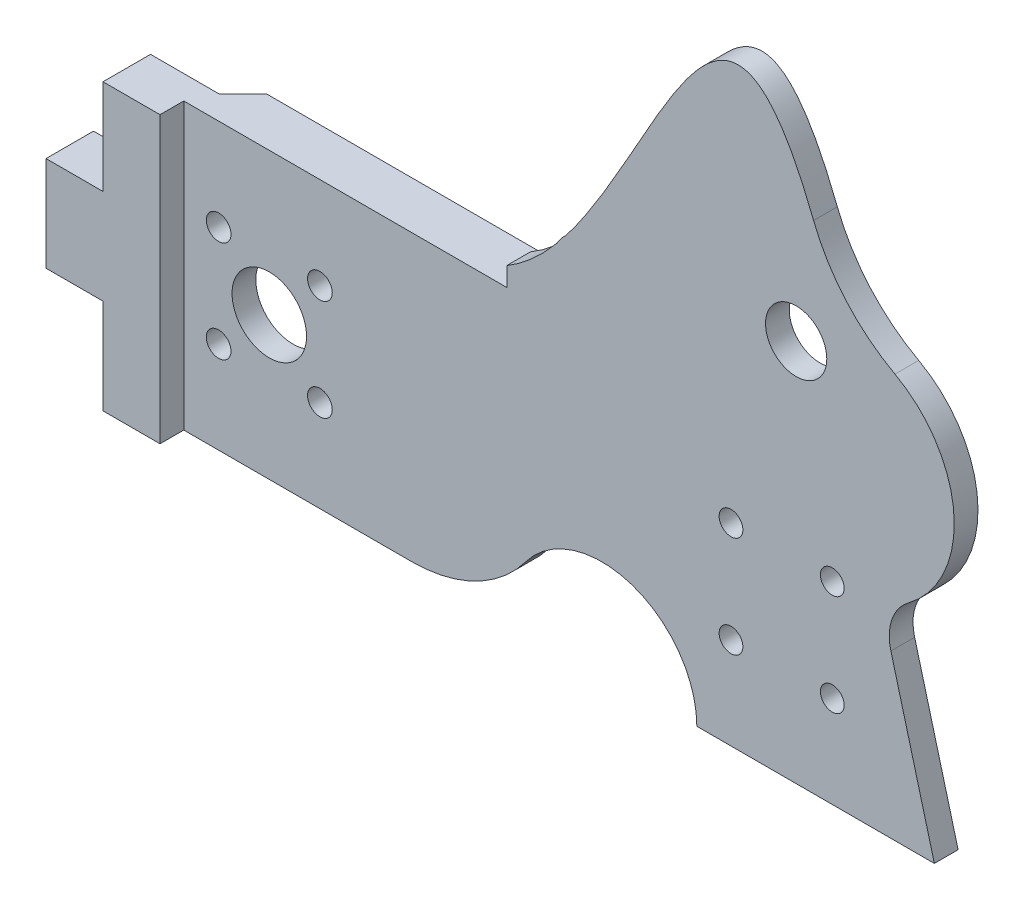
SolidWorks part; units mm, degrees
ref_plane "Front Plane" through (0, 0, 0) normal (0, 0, 1) x (1, 0, 0)
ref_plane "Top Plane" through (0, 0, 0) normal (0, 1, 0) x (1, 0, 0)
ref_plane "Right Plane" through (0, 0, 0) normal (1, 0, 0) x (0, 0, -1)
sketch "Sketch1" plane through (0, 0, 0) normal (0, 0, 1) x (1, 0, 0)
  line L0 (0, 0) -> (107.95, 0)
  line L3 (0, 38.1) -> (0, 25.4)
  line L4 (95.3675, 55.88) -> (0, 38.1)
  line L5 (0, 19.05) -> (100.2273, 19.05) construction
  line L6 (19.05, 19.05) -> (19.05, 28.62) construction
  line L7 (19.05, 19.05) -> (25.817, 25.817) construction
  line L8 (107.95, 0) -> (100.9363, 26.1756)
  line L10 (0, 12.7) -> (0, 0)
  line L11 (0, 25.4) -> (-7.62, 25.4)
  line L13 (0, 12.7) -> (-7.62, 12.7)
  line L14 (-7.62, 25.4) -> (-7.62, 12.7)
  line L15 (100.9363, 26.1756) -> (100.8688, 26.4276)
  arc A0 (100.8688, 26.4276) -> (95.3675, 55.88) centre (95.3675, 40.64) ccw
  circle A1 centre (95.3675, 40.64) radius 4.0957 construction
  circle A2 centre (19.05, 19.05) radius 9.57 construction
  circle A3 centre (25.817, 25.817) radius 1.651
  circle A4 centre (25.817, 12.283) radius 1.651
  circle A5 centre (12.283, 12.283) radius 1.651
  circle A6 centre (12.283, 25.817) radius 1.651
  point P26 (19.05, 19.05)
  dimension "D1" = 8.1915
  dimension "D5" = 15.24
  dimension "D4" = 19.14
  dimension "D7" = 3.302
  dimension "D11" = 97.0107
  dimension "D2" = 38.1
  dimension "D3" = 40.64
  dimension "D6" = 107.95
  dimension "D8" = 45
  dimension "D9" = 4
  dimension "D10" = 19.05
  dimension "D12" = 75
  dimension "D14" = 12.7
  dimension "D15" = 12.7
  dimension "D16" = 7.62
extrude "Boss-Extrude1" add sketch "Sketch1" along normal blind 3.175
sketch "Sketch2" plane through (0, 0, 3.175) normal (0, 0, 1) x (1, 0, 0)
  circle A0 centre (95.3675, 40.64) radius 38.1 construction
sketch "Sketch6" plane through (0, 0, 3.175) normal (0, 0, 1) x (1, 0, 0)
  line L0 (0, 0) -> (107.95, 0) construction
  line L1 (50.8, 0) -> (76.2, 0)
  arc A0 (76.2, 0) -> (50.8, 0) centre (63.5, 0) ccw
  dimension "D1" = 25.4
  dimension "D2" = 31.75
extrude "Cut-Extrude2" cut sketch "Sketch6" against normal blind 6.35
sketch "Sketch7" plane through (0, 0, 3.175) normal (0, 0, 1) x (1, 0, 0)
  line L0 (12.283, 25.817) -> (25.817, 12.283) construction
  line L1 (12.283, 12.283) -> (25.817, 25.817) construction
  line L2 (12.283, 25.817) -> (78.4839, 25.817) construction
  line L3 (11.7326, 12.283) -> (12.283, 12.283) construction
  circle A0 centre (19.05, 19.05) radius 4.9784
  circle A4 centre (80.7666, 12.283) radius 1.5875
  circle A5 centre (94.2997, 12.283) radius 1.5875
  circle A6 centre (80.7666, 25.817) radius 1.5875
  circle A7 centre (94.2997, 25.817) radius 1.5875
  dimension "D1" = 9.9568
  dimension "D2" = 3.175
  dimension "D3" = 13.5331
extrude "Cut-Extrude3" cut sketch "Sketch7" against normal through all
fillet "Fillet1" radius 6.35 1 edges at (100.8688, 26.4276, 1.5875)
sketch "Sketch8" plane through (0, 0, 3.175) normal (0, 0, 1) x (1, 0, 0)
  line L1 (0, 38.1) -> (50.8, 38.1)
  line L2 (0, 38.1) -> (0, 50.8)
  line L3 (0, 50.8) -> (50.8, 50.8)
  line L4 (50.8, 38.1) -> (50.8, 50.8)
  dimension "D1" = 50.8
  dimension "D2" = 12.7
extrude "Cut-Extrude4" cut sketch "Sketch8" against normal blind 50.8
sketch "Sketch9" plane through (0, 0, 3.175) normal (0, 0, 1) x (1, 0, 0)
  line L3 (50.8, 40.64) -> (57.15, 40.64)
  line L5 (57.15, 40.64) -> (50.8, 40.64)
  line L6 (57.15, 40.64) -> (57.15, 50.8)
  line L7 (57.15, 50.8) -> (50.8, 50.8)
  line L8 (50.8, 40.64) -> (50.8, 50.8)
  line L9 (0, 38.1) -> (50.8, 38.1) construction
  line M8 (50.8, 47.571) -> (50.8, 38.1)
  line M21 (95.3675, 55.88) -> (50.8, 47.571)
  dimension "D1" = 10.16
  dimension "D2" = 2.54
  dimension "D3" = 6.35
extrude "Cut-Extrude5" cut sketch "Sketch9" against normal blind 19.304 contours L3 L6 M21 M8 region at (54.0583, 44.4092, 3.175)
fillet "Fillet6" radius 6.35 1 edges at (57.15, 40.64, 1.5875)
fillet "Fillet7" radius 6.35 1 edges at (57.15, 48.7549, 1.5875)
fillet "Fillet8" radius 19.05 1 edges at (50.8, 0, 1.5875)
sketch "Sketch12" plane through (0, 0, 3.175) normal (0, 0, 1) x (1, 0, 0)
  line L0 (107.95, 0) -> (146.812, 0) construction
  line L1 (8.0257, 45.4128) -> (80.6683, 75.7903) construction
  line L2 (95.3675, 40.64) -> (80.6683, 75.7903) construction
  line L3 (80.6683, 75.7903) -> (79.4434, 78.7195) construction
  line L4 (50.8, 40.64) -> (85.0271, 40.64)
  line L5 (85.0271, 40.64) -> (95.3675, 55.88)
  arc A0 (61.8128, 49.6242) -> (56.8883, 45.1859) centre (62.9766, 43.3817) ccw construction
  circle A1 centre (19.05, 19.05) radius 28.575 construction
  circle A2 centre (95.3675, 40.64) radius 38.1 construction
  circle A3 centre (80.6683, 75.7903) radius 3.175 construction
  spline S0 degree 3 poles (50.8, 40.64) (70.7778, 52.1788) (78.5943, 111.5434) (95.3675, 55.88) knots 0 0 0 0 1 1 1 1
  dimension "D2" = 6.35
  dimension "D1" = 38.862
extrude "Boss-Extrude2" add sketch "Sketch12" against normal blind 3.175
fillet "Fillet9" radius 24.13 1 edges at (95.3675, 55.88, 1.5875)
sketch "Sketch13" plane through (0, 0, 0) normal (0, 0, -1) x (-1, 0, 0)
  line L1 (-50.8, 38.1) -> (-9.1321, 38.1)
  line L2 (-50.8, 38.1) -> (-50.8, 28.6404)
  line L3 (-50.8, 28.6404) -> (-9.1321, 28.6404)
  line L6 (-9.1321, 8.4682) -> (-38.1, 8.4682)
  line L7 (-9.1321, 8.4682) -> (-9.1321, 0)
  line L8 (-9.1321, 0) -> (-38.1, 0)
  line L9 (-38.1, 8.4682) -> (-38.1, 0)
  line L10 (-9.1321, 38.1) -> (-9.1321, 28.6404)
extrude "Boss-Extrude3" add sketch "Sketch13" along normal blind 3.175
sketch "Sketch16" plane through (0, 0, 3.175) normal (0, 0, 1) x (1, 0, 0)
  circle A0 centre (89.4737, 51.217) radius 4.0958
  circle A1 centre (94.2997, 25.817) radius 1.5875 construction
  dimension "D1" = 25.4
  dimension "D2" = 4.826
extrude "Cut-Extrude8" cut sketch "Sketch16" against normal through all
sketch "Sketch18" plane through (0, 0, 3.175) normal (0, 0, 1) x (1, 0, 0)
  line L0 (0, 0) -> (7.62, 0)
  line L1 (0, 0) -> (38.1, 0) construction
  line L2 (7.62, 0) -> (7.62, 38.1)
  line L3 (0, 38.1) -> (50.8, 38.1) construction
  line L4 (7.62, 38.1) -> (0, 38.1)
  line L5 (0, 38.1) -> (0, 25.4)
  line L6 (0, 25.4) -> (-7.62, 25.4)
  line L7 (-7.62, 25.4) -> (-7.62, 12.7)
  line L8 (-7.62, 12.7) -> (0, 12.7)
  line L9 (0, 12.7) -> (0, 0)
  dimension "D1" = 7.62
extrude "Boss-Extrude4" add sketch "Sketch18" along normal blind 3.175
sketch "Sketch19" plane through (0, 38.1, 0) normal (0, 1, 0) x (1, 0, 0)
  line L0 (9.1321, 0) -> (12.3071, 3.175)
  line L1 (9.1321, 3.175) -> (50.8, 3.175) construction
  line L2 (9.1321, 3.175) -> (9.1321, 0) construction
  line L3 (12.3071, 3.175) -> (9.1321, 3.175)
  line L4 (9.1321, 3.175) -> (9.1321, 0)
  dimension "D1" = 45
extrude "Cut-Extrude9" cut sketch "Sketch19" against normal through all
